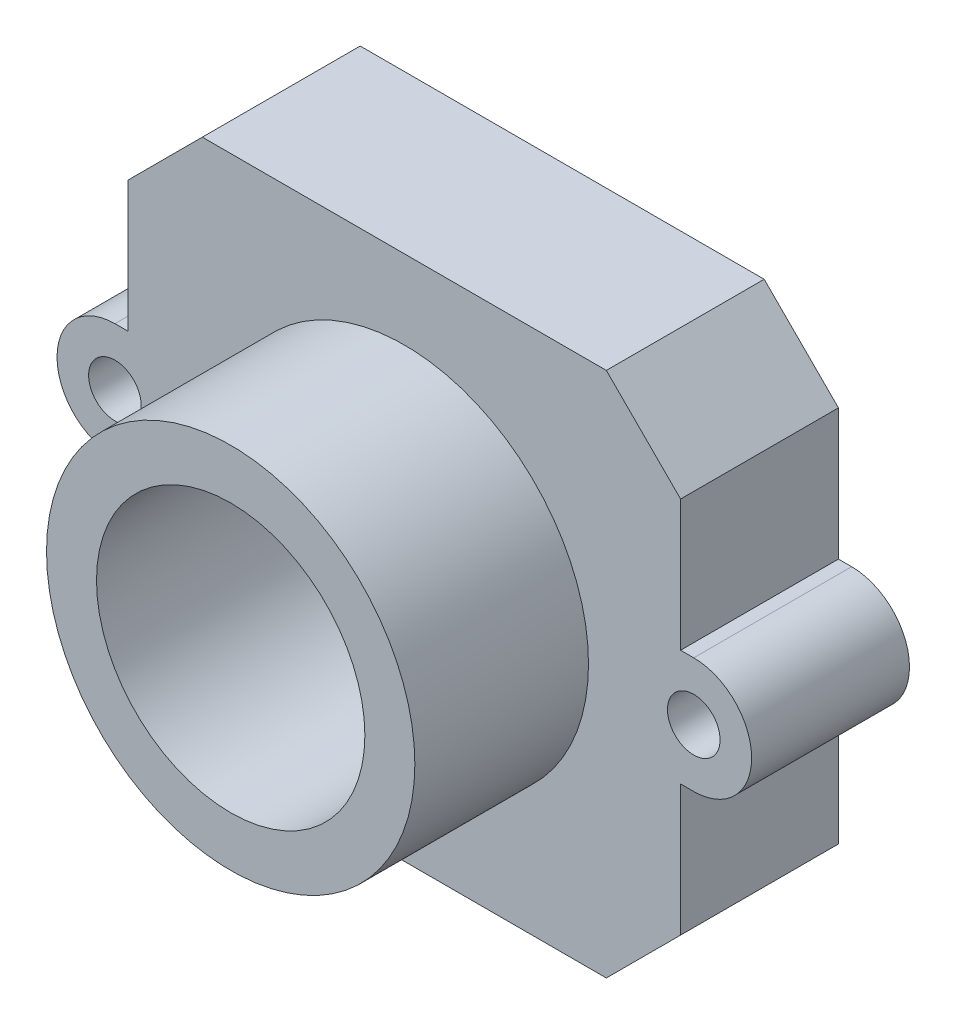
SolidWorks part; units mm, degrees
ref_plane "Front" through (0, 0, 0) normal (0, 0, 1) x (1, 0, 0)
ref_plane "Top" through (0, 0, 0) normal (0, 1, 0) x (1, 0, 0)
ref_plane "Right" through (0, 0, 0) normal (1, 0, 0) x (0, 0, -1)
sketch "Sketch1" plane through (0, 0, 0) normal (0, 0, 1) x (1, 0, 0)
  line L0 (-10.5, 7.1777) -> (-7.6777, 10)
  line L1 (-10.5, 10) -> (10.5, 10)
  line L2 (-10.5, 10) -> (-10.5, -10)
  line L3 (-10.5, -10) -> (10.5, -10)
  line L4 (10.5, 10) -> (10.5, -10)
  line L5 (7.6777, 10) -> (10.5, 7.1777)
  line L6 (-10.5, -7.1777) -> (-7.6777, -10)
  line L7 (7.6777, -10) -> (10.5, -7.1777)
  line L8 (10.5, 2.2) -> (11, 2.2)
  line L9 (10.5, -2.2) -> (11, -2.2)
  line L10 (-10.5, 2.2) -> (-11, 2.2)
  line L11 (-10.5, -2.2) -> (-11, -2.2)
  line L12 (-9, 6.5563) -> (-9, -6.5563)
  line L13 (-9, -6.5563) -> (-7.0563, -8.5)
  line L14 (-7.0563, -8.5) -> (7.0563, -8.5)
  line L15 (7.0563, -8.5) -> (9, -6.5563)
  line L16 (9, -6.5563) -> (9, 6.5563)
  line L17 (9, 6.5563) -> (7.0563, 8.5)
  line L18 (7.0563, 8.5) -> (-7.0563, 8.5)
  line L19 (-7.0563, 8.5) -> (-9, 6.5563)
  arc A0 (11, 2.2) -> (11, -2.2) centre (11, 0) cw
  arc A1 (-11, -2.2) -> (-11, 2.2) centre (-11, 0) cw
  circle A2 centre (-11, 0) radius 1
  circle A3 centre (11, 0) radius 1
  point P4 (0, 10)
  point P5 (10.5, 0)
  dimension "D4" = 2.2
  dimension "D5" = 2.2
  dimension "D7" = 2
  dimension "D8" = 2
  dimension "D1" = 25
  dimension "D2" = 21
  dimension "D3" = 20
  dimension "D6" = 11
  dimension "D9" = 11
  dimension "D10" = 1.5
  dimension "D11" = 1.5
  dimension "D12" = 1.5
  dimension "D13" = 1.5
  dimension "D14" = 1.5
  dimension "D15" = 1.5
  dimension "D16" = 1.5
  dimension "D17" = 1.5
extrude "Roof" add sketch "Sketch1" along normal blind 1 contours L3 L7 L4 L5 L1 L0 L2 L6 L19 L18 L17 L16 L15 L14 L13 L12 | L18 L19 L12 L13 L14 L15 L16 L17 | A1 L11 L2 L10 A2 | A0 L8 L4 L9 A3 region at (-8.8838, 8.3838, 0) region at (-10.5516, 1.533, 0) region at (10.75, 2.1484, 0) region at (0, 0, 0)
extrude "Walls" add sketch "Sketch1<3>" against normal blind 5 contours L3 L7 L4 L5 L1 L0 L2 L6 L19 L18 L17 L16 L15 L14 L13 L12 | A0 L8 L4 L9 A3 | A1 L11 L2 L10 A2 region at (-8.8838, 8.3838, 0) region at (-10.5516, 1.533, 0) region at (10.75, 2.1484, 0)
sketch "Sketch1<3>" plane through (0, 0, 0) normal (0, 0, 1) x (1, 0, 0) same geometry as "Sketch1"
sketch "Sketch2" plane through (0, 0, 1) normal (0, 0, 1) x (1, 0, 0)
  circle A0 centre (0, 0) radius 5.1
  circle A1 centre (0, 0) radius 7
  dimension "D1" = 14
  dimension "D2" = 10.2
extrude "Screw hole in roof" cut sketch "Sketch2" against normal through all contours A0 region at (0, 0, 1)
extrude "Screw holder" add sketch "Sketch2<3>" along normal blind 6.6
sketch "Sketch2<3>" plane through (0, 0, 1) normal (0, 0, 1) x (1, 0, 0) same geometry as "Sketch2"
